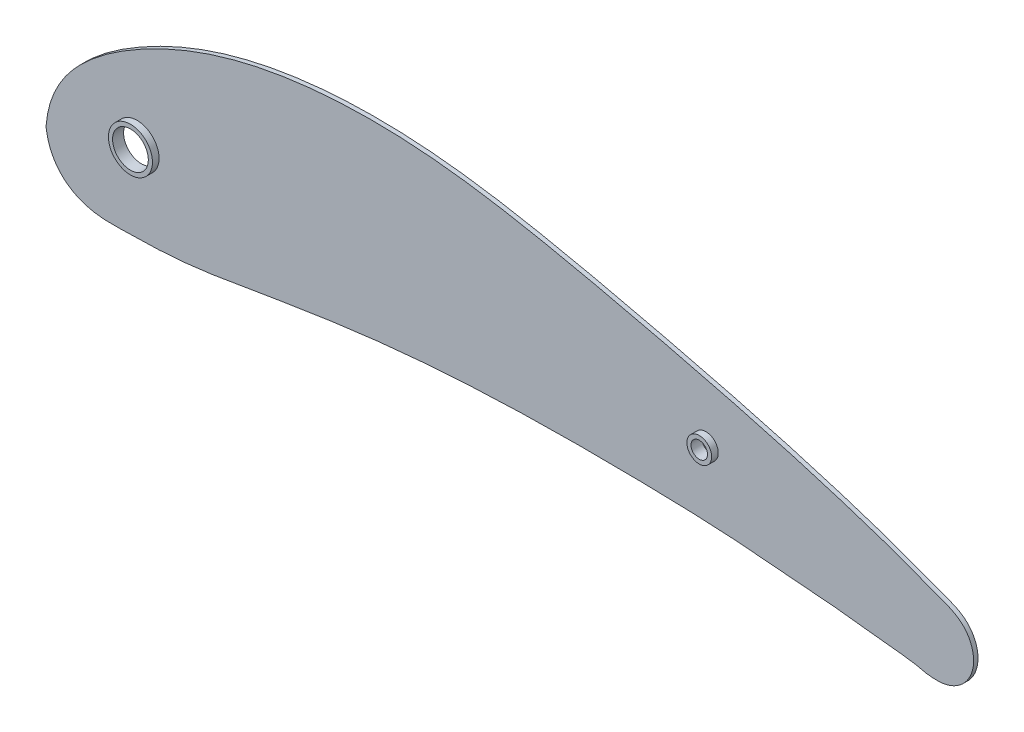
SolidWorks part; units mm, degrees
material "ABS"
ref_plane "Front Plane" through (0, 0, 0) normal (0, 0, 1) x (1, 0, 0)
ref_plane "Top Plane" through (0, 0, 0) normal (0, 1, 0) x (1, 0, 0)
ref_plane "Right Plane" through (0, 0, 0) normal (1, 0, 0) x (0, 0, -1)
sketch "Sketch1" plane through (0, 0, 0) normal (0, 0, 1) x (1, 0, 0)
  spline S0 degree 3 poles (0.0006, 0.0001) (0.8106, 7.3592) (8.6491, 17.8566) (26.2867, 29.9752) (52.1111, 42.0692) (89.5976, 49.2908) (131.4008, 47.8848) (173.2567, 40.0411) (217.9611, 29.613) (256.9521, 19.5289) (290.3598, 8.711) (301.2732, 4.3828) (314.8169, -0.5162) (309.8463, 0.0001) knots 0 0 0 0 0.060864 0.113688 0.188609 0.312909 0.448482 0.557612 0.691544 0.852438 0.929756 0.976058 1 1 1 1
  spline S1 degree 3 poles (309.8463, 0.0001) (303.9568, 1.471) (293.9895, 2.094) (276.264, 4.5144) (260.8463, 5.4274) (235.8588, 7.8703) (205.1014, 8.8381) (157.7186, 9.0307) (110.4973, 6.1815) (66.5062, -0.5867) (36.4547, -6.0985) (15.3166, -6.1891) (1.2307, -6.9241) (0.0006, 0.0001) knots 0 0 0 0 0.057787 0.095275 0.171021 0.205339 0.335319 0.464904 0.658702 0.785512 0.893517 0.943092 1 1 1 1
extrude "Boss-Extrude1" add sketch "Sketch1" along normal blind 1.5875
sketch "Sketch2" plane through (0, 0, 1.5875) normal (0, 0, 1) x (1, 0, 0)
  circle A0 centre (20.32, 10.16) radius 6.5
  circle A1 centre (227.2963, 19.0501) radius 3
  circle A2 centre (20.32, 10.16) radius 5.75
  circle A3 centre (20.32, 10.16) radius 8
  circle A4 centre (227.2963, 19.0501) radius 4.5
  circle A5 centre (227.2963, 19.0501) radius 2.5
  dimension "D2" = 13
  dimension "D3" = 6
  dimension "D6" = 20.32
  dimension "D7" = 1.5
  dimension "D8" = 11.5
  dimension "D9" = 5
  dimension "D10" = 1.5
  dimension "D1" = 82.55
  dimension "D4" = 19.05
  dimension "D5" = 10.16
extrude "Boss-Extrude2" add sketch "Sketch2" along normal blind 2.4125 contours A4 A1 | A3 A0 region at (12.5463, 10.16, 1.5875) region at (222.9236, 19.0501, 1.5875)
extrude "Cut-Extrude1" cut sketch "Sketch2<4>" against normal blind 4 contours A2 | A0 A2 | A1 region at (14.0038, 10.16, 1.5875) region at (20.32, 10.16, 1.5875)
sketch "Sketch2<4>" plane through (0, 0, 1.5875) normal (0, 0, 1) x (1, 0, 0) same geometry as "Sketch2"
sketch "Sketch3" plane through (0, 0, 0) normal (0, 0, -1) x (-1, 0, 0)
  circle A0 centre (-227.2963, 19.0501) radius 3
  circle A1 centre (-20.32, 10.16) radius 6.5
  spline S4 degree 3 poles (-794.818, 3953.6273) (-366.3145, -67.9731) (-338.3359, -19.8467) (-305.9476, -12.1233) (-305.5233, -12.0295) (-304.2487, -11.7666) (-303.3965, -11.6156) (-300.8352, -11.213) (-299.1211, -11.0104) (-295.689, -10.6461) (-293.9708, -10.4848) (-291.3954, -10.2247) (-290.5373, -10.1347) (-288.822, -9.9442) (-287.9649, -9.8444) (-285.3941, -9.5376) (-283.6812, -9.3228) (-280.254, -8.9085) (-278.5394, -8.7116) (-273.3892, -8.1853) (-269.9489, -7.9035) (-263.0656, -7.3675) (-259.6226, -7.1135) (-252.7436, -6.5343) (-249.3084, -6.2011) (-242.431, -5.6059) (-238.9878, -5.3542) (-232.0935, -4.9305) (-228.6415, -4.7575) (-218.2859, -4.3276) (-211.3818, -4.1597) (-197.5731, -3.918) (-190.6686, -3.8461) (-176.8592, -3.8453) (-169.9542, -3.9165) (-156.1436, -4.2469) (-149.2349, -4.5055) (-135.4369, -5.2363) (-128.547, -5.7084) (-114.7879, -6.8956) (-107.9189, -7.6126) (-94.2037, -9.3155) (-87.359, -10.2944) (-77.1158, -11.889) (-73.7047, -12.4417) (-66.8874, -13.5783) (-63.482, -14.1674) (-53.262, -15.9097) (-46.4424, -17.0289) (-37.8533, -17.9873) (-36.1323, -18.1567) (-32.6884, -18.4393) (-30.9647, -18.5506) (-25.7891, -18.7998) (-22.3328, -18.8616) (-18.0138, -18.9646) (-17.15, -18.9864) (-15.4226, -19.0355) (-14.559, -19.065) (-12.8314, -19.1079) (-11.9674, -19.1211) (-10.2388, -19.1103) (-9.3743, -19.0865) (-6.8, -18.9358) (-5.1041, -18.7297) (-2.6061, -18.1813) (-1.781, -17.9588) (-0.5569, -17.5549) (-0.1511, -17.4087) (0.6556, -17.0908) (1.0582, -16.9184) (3.0336, -15.9992) (4.4968, -15.0839) (6.1651, -13.6925) (6.4918, -13.4006) (7.122, -12.7971) (7.425, -12.4861) (8.2983, -11.5259) (8.8331, -10.8497) (9.5651, -9.782) (9.7973, -9.4172) (10.2382, -8.6696) (10.4474, -8.2857) (11.035, -7.1145) (11.3705, -6.3152) (11.9375, -4.6822) (12.169, -3.8486) (12.4425, -2.5739) (12.5175, -2.1436) (245.8952, 1311.4772) (479.1966, 2624.6682) (712.4984, 3937.861) knots -0.290887 -0.290887 -0.290887 -0.290887 0.003906 0.003906 0.007813 0.007813 0.015625 0.015625 0.03125 0.03125 0.046875 0.046875 0.054688 0.054688 0.0625 0.0625 0.078125 0.078125 0.09375 0.09375 0.125 0.125 0.15625 0.15625 0.1875 0.1875 0.21875 0.21875 0.25 0.25 0.3125 0.3125 0.375 0.375 0.4375 0.4375 0.5 0.5 0.5625 0.5625 0.625 0.625 0.6875 0.6875 0.71875 0.71875 0.75 0.75 0.8125 0.8125 0.828125 0.828125 0.84375 0.84375 0.875 0.875 0.882813 0.882813 0.890625 0.890625 0.898438 0.898438 0.90625 0.90625 0.921875 0.921875 0.929688 0.929688 0.933594 0.933594 0.9375 0.9375 0.953125 0.953125 0.957031 0.957031 0.960938 0.960938 0.96875 0.96875 0.972656 0.972656 0.976563 0.976563 0.984375 0.984375 0.992188 0.992188 0.996094 0.996094 12.931027 12.931027 12.931027 12.931027 only from (-307.6407, -12.5391) to (12.8229, -0.4244)
  spline S5 degree 3 poles (450.4865, -3976.3582) (304.5409, -2650.5224) (158.5953, -1324.6865) (12.5919, 1.6739) (12.5289, 2.1971) (12.2979, 3.7557) (12.0986, 4.783) (11.3667, 7.8296) (10.7001, 9.8139) (9.6458, 12.2364) (9.4233, 12.7191) (8.9589, 13.6734) (8.2345, 15.0856) (7.4307, 16.4423) (5.7262, 19.088) (4.4608, 20.7616) (2.4032, 23.1605) (1.6888, 23.9434) (0.222, 25.4669) (-2.0301, 27.684) (-4.4106, 29.7332) (-9.3168, 33.6415) (-12.7815, 35.993) (-18.1647, 39.2766) (-19.9904, 40.3334) (-23.6661, 42.358) (-25.5203, 43.3273) (-31.1305, 46.109) (-34.9342, 47.7954) (-46.5315, 52.3626) (-54.5152, 54.7412) (-63.7448, 56.7617) (-64.7747, 56.9772) (-66.8348, 57.3892) (-69.9258, 57.9785) (-73.0196, 58.4848) (-79.2106, 59.3934) (-83.3425, 59.8608) (-95.7504, 60.8925) (-104.0386, 61.0863) (-116.492, 60.7375) (-120.6467, 60.5145) (-126.8836, 60.0306) (-128.9634, 59.8445) (-133.1246, 59.4241) (-135.2075, 59.1895) (-145.595, 57.9058) (-153.8328, 56.5247) (-166.1326, 54.1736) (-170.223, 53.3435) (-178.3938, 51.633) (-182.4737, 50.7513) (-194.7, 48.0394) (-202.8328, 46.1427) (-215.0143, 43.2113) (-219.0722, 42.221) (-227.1821, 40.2119) (-231.2322, 39.1918) (-243.362, 36.0642) (-251.4202, 33.8872) (-263.4483, 30.4288) (-267.4479, 29.2444) (-275.4266, 26.8089) (-279.4062, 25.5593) (-285.3572, 23.6252) (-287.3377, 22.9703) (-291.2905, 21.6338) (-293.2629, 20.9523) (-297.195, 19.5486) (-299.1532, 18.8211) (-303.0645, 17.3496) (-305.019, 16.6102) (-307.9551, 15.5148) (-308.9343, 15.1515) (-310.8939, 14.4286) (-311.8752, 14.0719) (-313.8314, 13.3379) (-314.808, 12.9614) (-316.7192, 12.1265) (-317.6523, 11.6639) (-318.978, 10.8209) (-319.4082, 10.5149) (-320.2258, 9.8596) (-320.6153, 9.5093) (-321.3536, 8.7611) (-321.6995, 8.3658) (-322.3367, 7.5434) (-322.6295, 7.1149) (-323.1632, 6.2229) (-323.4044, 5.7588) (-323.8312, 4.7968) (-324.1948, 3.8185) (-324.4364, 2.809) (-324.5716, 2.0401) (-324.6089, 1.7818) (-324.6679, 1.2612) (-324.6896, 0.9981) (-324.7567, -0.3109) (-324.6826, -1.3467) (-324.3823, -2.8833) (-324.249, -3.3956) (-323.9242, -4.3886) (-323.541, -5.3551) (-323.0431, -6.2692) (-322.6256, -6.9348) (-322.4785, -7.1539) (-322.1729, -7.5802) (-322.0142, -7.7878) (-321.1922, -8.7978) (-320.4439, -9.5189) (-318.7612, -10.7826) (-317.8577, -11.3014) (-316.4211, -11.9133) (-315.9254, -12.0903) (-314.9178, -12.3839) (-314.4094, -12.4998) (-313.384, -12.6741) (-312.867, -12.7323) (-311.8251, -12.7968) (-311.2988, -12.8028) (-310.2504, -12.7747) (-309.7275, -12.7412) (-275.8665, -9.8118) (-245.9968, 43.8257) (63.2429, -3989.5034) knots -9.868844 -9.868844 -9.868844 -9.868844 0.003906 0.003906 0.007813 0.007813 0.015625 0.015625 0.03125 0.03125 0.035156 0.035156 0.039063 0.046875 0.046875 0.0625 0.0625 0.070313 0.070313 0.078125 0.09375 0.09375 0.125 0.125 0.140625 0.140625 0.15625 0.15625 0.1875 0.1875 0.25 0.25 0.257813 0.257813 0.265625 0.28125 0.28125 0.3125 0.3125 0.375 0.375 0.40625 0.40625 0.421875 0.421875 0.4375 0.4375 0.5 0.5 0.53125 0.53125 0.5625 0.5625 0.625 0.625 0.65625 0.65625 0.6875 0.6875 0.75 0.75 0.78125 0.78125 0.8125 0.8125 0.828125 0.828125 0.84375 0.84375 0.859375 0.859375 0.875 0.875 0.882813 0.882813 0.890625 0.890625 0.898438 0.898438 0.90625 0.90625 0.910156 0.910156 0.914063 0.914063 0.917969 0.917969 0.921875 0.921875 0.925781 0.925781 0.929688 0.933594 0.933594 0.935547 0.935547 0.9375 0.9375 0.945313 0.945313 0.949219 0.949219 0.953125 0.957031 0.957031 0.958984 0.958984 0.960938 0.960938 0.96875 0.96875 0.976563 0.976563 0.980469 0.980469 0.984375 0.984375 0.988281 0.988281 0.992188 0.992188 0.996094 0.996094 1.245538 1.245538 1.245538 1.245538 only from (12.8229, -0.4244) to (-307.6407, -12.5391)
  spline S6 degree 3 poles (-307.6407, -12.5391) (-307.2176, -12.4334) (-306.7947, -12.3253) (-305.9476, -12.1233) (-305.5233, -12.0295) (-304.2487, -11.7666) (-303.3965, -11.6156) (-300.8352, -11.213) (-299.1211, -11.0104) (-295.689, -10.6461) (-293.9708, -10.4848) (-291.3954, -10.2247) (-290.5373, -10.1347) (-288.822, -9.9442) (-287.9649, -9.8444) (-285.3941, -9.5376) (-283.6812, -9.3228) (-280.254, -8.9085) (-278.5394, -8.7116) (-273.3892, -8.1853) (-269.9489, -7.9035) (-263.0656, -7.3675) (-259.6226, -7.1135) (-252.7436, -6.5343) (-249.3084, -6.2011) (-242.431, -5.6059) (-238.9878, -5.3542) (-232.0935, -4.9305) (-228.6415, -4.7575) (-218.2859, -4.3276) (-211.3818, -4.1597) (-197.5731, -3.918) (-190.6686, -3.8461) (-176.8592, -3.8453) (-169.9542, -3.9165) (-156.1436, -4.2469) (-149.2349, -4.5055) (-135.4369, -5.2363) (-128.547, -5.7084) (-114.7879, -6.8956) (-107.9189, -7.6126) (-94.2037, -9.3155) (-87.359, -10.2944) (-77.1158, -11.889) (-73.7047, -12.4417) (-66.8874, -13.5783) (-63.482, -14.1674) (-53.262, -15.9097) (-46.4424, -17.0289) (-37.8533, -17.9873) (-36.1323, -18.1567) (-32.6884, -18.4393) (-30.9647, -18.5506) (-25.7891, -18.7998) (-22.3328, -18.8616) (-18.0138, -18.9646) (-17.15, -18.9864) (-15.4226, -19.0355) (-14.559, -19.065) (-12.8314, -19.1079) (-11.9674, -19.1211) (-10.2388, -19.1103) (-9.3743, -19.0865) (-6.8, -18.9358) (-5.1041, -18.7297) (-2.6061, -18.1813) (-1.781, -17.9588) (-0.5569, -17.5549) (-0.1511, -17.4087) (0.6556, -17.0908) (1.0582, -16.9184) (3.0336, -15.9992) (4.4968, -15.0839) (6.1651, -13.6925) (6.4918, -13.4006) (7.122, -12.7971) (7.425, -12.4861) (8.2983, -11.5259) (8.8331, -10.8497) (9.5651, -9.782) (9.7973, -9.4172) (10.2382, -8.6696) (10.4474, -8.2857) (11.035, -7.1145) (11.3705, -6.3152) (11.9375, -4.6822) (12.169, -3.8486) (12.4425, -2.5739) (12.5175, -2.1436) (12.6702, -1.284) (12.7465, -0.8542) (12.8229, -0.4244) knots 0 0 0 0 0.003906 0.003906 0.007813 0.007813 0.015625 0.015625 0.03125 0.03125 0.046875 0.046875 0.054688 0.054688 0.0625 0.0625 0.078125 0.078125 0.09375 0.09375 0.125 0.125 0.15625 0.15625 0.1875 0.1875 0.21875 0.21875 0.25 0.25 0.3125 0.3125 0.375 0.375 0.4375 0.4375 0.5 0.5 0.5625 0.5625 0.625 0.625 0.6875 0.6875 0.71875 0.71875 0.75 0.75 0.8125 0.8125 0.828125 0.828125 0.84375 0.84375 0.875 0.875 0.882813 0.882813 0.890625 0.890625 0.898438 0.898438 0.90625 0.90625 0.921875 0.921875 0.929688 0.929688 0.933594 0.933594 0.9375 0.9375 0.953125 0.953125 0.957031 0.957031 0.960938 0.960938 0.96875 0.96875 0.972656 0.972656 0.976563 0.976563 0.984375 0.984375 0.992188 0.992188 0.996094 0.996094 1 1 1 1
  spline S7 degree 3 poles (12.8229, -0.4244) (12.7651, 0.1002) (12.7074, 0.6248) (12.5919, 1.6739) (12.5289, 2.1971) (12.2979, 3.7557) (12.0986, 4.783) (11.3667, 7.8296) (10.7001, 9.8139) (9.6458, 12.2364) (9.4233, 12.7191) (8.9589, 13.6734) (8.2345, 15.0856) (7.4307, 16.4423) (5.7262, 19.088) (4.4608, 20.7616) (2.4032, 23.1605) (1.6888, 23.9434) (0.222, 25.4669) (-2.0301, 27.684) (-4.4106, 29.7332) (-9.3168, 33.6415) (-12.7815, 35.993) (-18.1647, 39.2766) (-19.9904, 40.3334) (-23.6661, 42.358) (-25.5203, 43.3273) (-31.1305, 46.109) (-34.9342, 47.7954) (-46.5315, 52.3626) (-54.5152, 54.7412) (-63.7448, 56.7617) (-64.7747, 56.9772) (-66.8348, 57.3892) (-69.9258, 57.9785) (-73.0196, 58.4848) (-79.2106, 59.3934) (-83.3425, 59.8608) (-95.7504, 60.8925) (-104.0386, 61.0863) (-116.492, 60.7375) (-120.6467, 60.5145) (-126.8836, 60.0306) (-128.9634, 59.8445) (-133.1246, 59.4241) (-135.2075, 59.1895) (-145.595, 57.9058) (-153.8328, 56.5247) (-166.1326, 54.1736) (-170.223, 53.3435) (-178.3938, 51.633) (-182.4737, 50.7513) (-194.7, 48.0394) (-202.8328, 46.1427) (-215.0143, 43.2113) (-219.0722, 42.221) (-227.1821, 40.2119) (-231.2322, 39.1918) (-243.362, 36.0642) (-251.4202, 33.8872) (-263.4483, 30.4288) (-267.4479, 29.2444) (-275.4266, 26.8089) (-279.4062, 25.5593) (-285.3572, 23.6252) (-287.3377, 22.9703) (-291.2905, 21.6338) (-293.2629, 20.9523) (-297.195, 19.5486) (-299.1532, 18.8211) (-303.0645, 17.3496) (-305.019, 16.6102) (-307.9551, 15.5148) (-308.9343, 15.1515) (-310.8939, 14.4286) (-311.8752, 14.0719) (-313.8314, 13.3379) (-314.808, 12.9614) (-316.7192, 12.1265) (-317.6523, 11.6639) (-318.978, 10.8209) (-319.4082, 10.5149) (-320.2258, 9.8596) (-320.6153, 9.5093) (-321.3536, 8.7611) (-321.6995, 8.3658) (-322.3367, 7.5434) (-322.6295, 7.1149) (-323.1632, 6.2229) (-323.4044, 5.7588) (-323.8312, 4.7968) (-324.1948, 3.8185) (-324.4364, 2.809) (-324.5716, 2.0401) (-324.6089, 1.7818) (-324.6679, 1.2612) (-324.6896, 0.9981) (-324.7567, -0.3109) (-324.6826, -1.3467) (-324.3823, -2.8833) (-324.249, -3.3956) (-323.9242, -4.3886) (-323.541, -5.3551) (-323.0431, -6.2692) (-322.6256, -6.9348) (-322.4785, -7.1539) (-322.1729, -7.5802) (-322.0142, -7.7878) (-321.1922, -8.7978) (-320.4439, -9.5189) (-318.7612, -10.7826) (-317.8577, -11.3014) (-316.4211, -11.9133) (-315.9254, -12.0903) (-314.9178, -12.3839) (-314.4094, -12.4998) (-313.384, -12.6741) (-312.867, -12.7323) (-311.8251, -12.7968) (-311.2988, -12.8028) (-310.2504, -12.7747) (-309.7275, -12.7412) (-308.6834, -12.6509) (-308.1621, -12.5933) (-307.6407, -12.5391) knots 0 0 0 0 0.003906 0.003906 0.007813 0.007813 0.015625 0.015625 0.03125 0.03125 0.035156 0.035156 0.039063 0.046875 0.046875 0.0625 0.0625 0.070313 0.070313 0.078125 0.09375 0.09375 0.125 0.125 0.140625 0.140625 0.15625 0.15625 0.1875 0.1875 0.25 0.25 0.257813 0.257813 0.265625 0.28125 0.28125 0.3125 0.3125 0.375 0.375 0.40625 0.40625 0.421875 0.421875 0.4375 0.4375 0.5 0.5 0.53125 0.53125 0.5625 0.5625 0.625 0.625 0.65625 0.65625 0.6875 0.6875 0.75 0.75 0.78125 0.78125 0.8125 0.8125 0.828125 0.828125 0.84375 0.84375 0.859375 0.859375 0.875 0.875 0.882813 0.882813 0.890625 0.890625 0.898438 0.898438 0.90625 0.90625 0.910156 0.910156 0.914063 0.914063 0.917969 0.917969 0.921875 0.921875 0.925781 0.925781 0.929688 0.933594 0.933594 0.935547 0.935547 0.9375 0.9375 0.945313 0.945313 0.949219 0.949219 0.953125 0.957031 0.957031 0.958984 0.958984 0.960938 0.960938 0.96875 0.96875 0.976563 0.976563 0.980469 0.980469 0.984375 0.984375 0.988281 0.988281 0.992188 0.992188 0.996094 0.996094 1 1 1 1
  dimension "D1" = 12.7
extrude "Boss-Extrude3" add sketch "Sketch3" against normal up to surface (1.5875 mm away) up to face at (12.32, 10.16, 1.5875)
